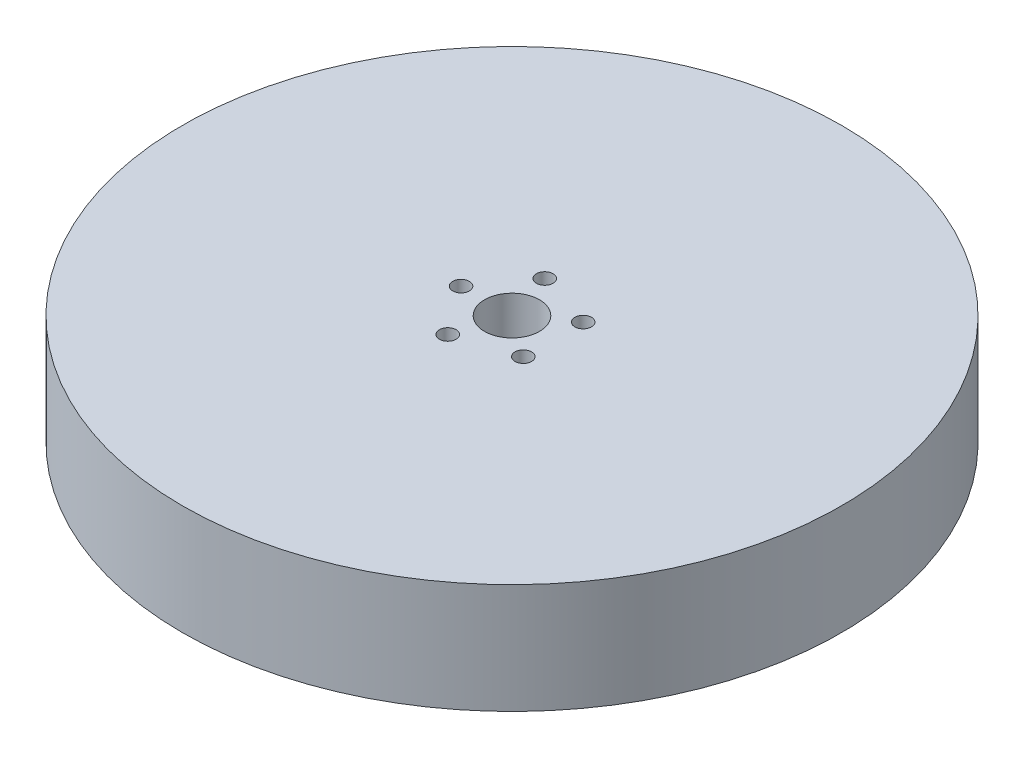
SolidWorks part; units mm, degrees
ref_plane "Front Plane" through (0, 0, 0) normal (0, 0, 1) x (1, 0, 0)
ref_plane "Top Plane" through (0, 0, 0) normal (0, 1, 0) x (1, 0, 0)
ref_plane "Right Plane" through (0, 0, 0) normal (1, 0, 0) x (0, 0, -1)
sketch "Sketch1" plane through (0, 0, 0) normal (0, 1, 0) x (1, 0, 0)
  circle A0 centre (0, 0) radius 90
  dimension "FLANGE_OD" = 180
extrude "Boss-Extrude1" add sketch "Sketch1" along normal blind 30
sketch "Sketch2" plane through (0, 0, 0) normal (0, 1, 0) x (1, 0, 0)
  circle A0 centre (0, 0) radius 7.5
  dimension "BORE_D" = 15
extrude "Cut-Extrude1" cut sketch "Sketch2" along normal through all
sketch "Sketch3" plane through (0, 30, 0) normal (0, 1, 0) x (1, 0, 0)
  circle A0 centre (0, 0) radius 13.9173 construction
  circle A1 centre (-13.9173, 0) radius 2.2772
  dimension "BOLT_D" = 4.5543
  dimension "BOLT_PCD" = 27.8346
extrude "Cut-Extrude2" cut sketch "Sketch3" against normal blind 23.0958
pattern_circular "CirPattern1" count 5 over 360 about axis through (0, 0, 0) along (0, 1, 0) of "Cut-Extrude2"
